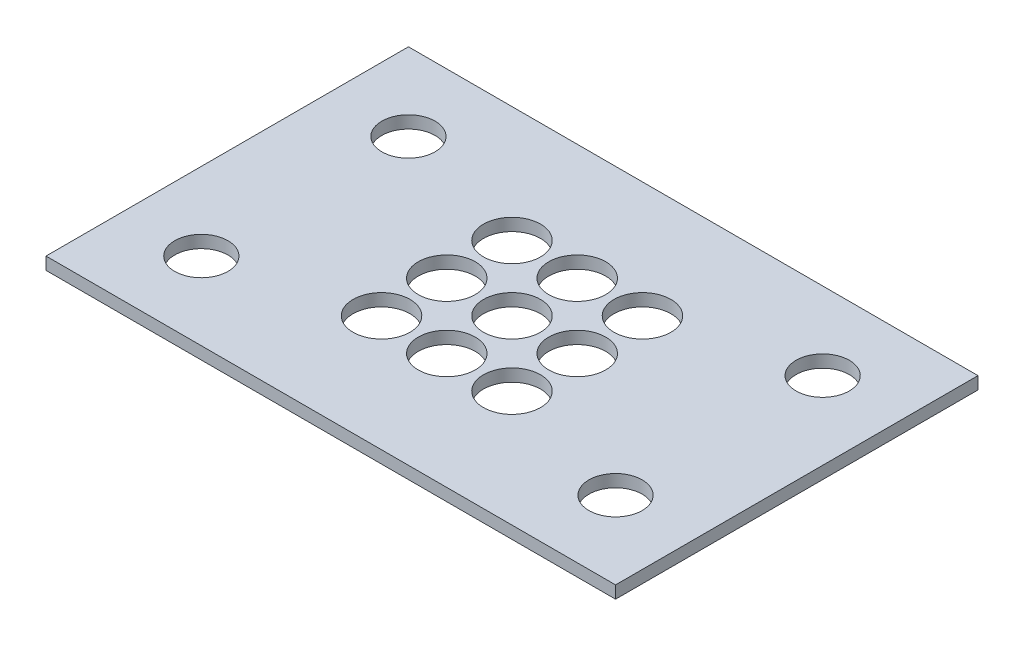
SolidWorks part; units mm, degrees
ref_plane "Front Plane" through (0, 0, 0) normal (0, 0, 1) x (1, 0, 0)
ref_plane "Top Plane" through (0, 0, 0) normal (0, 1, 0) x (1, 0, 0)
ref_plane "Right Plane" through (0, 0, 0) normal (1, 0, 0) x (0, 0, -1)
sketch "Sketch1" plane through (0, 0, 0) normal (0, 1, 0) x (1, 0, 0)
  line L0 (9.525, 34.925) -> (0, 34.925) construction
  line L1 (0, 0) -> (69.85, 0)
  line L2 (0, 0) -> (0, 44.45)
  line L3 (0, 44.45) -> (69.85, 44.45)
  line L4 (69.85, 0) -> (69.85, 44.45)
  line L5 (9.525, 34.925) -> (60.325, 34.925) construction
  line L6 (9.525, 34.925) -> (9.525, 9.525) construction
  line L7 (9.525, 9.525) -> (60.325, 9.525) construction
  line L8 (60.325, 34.925) -> (60.325, 9.525) construction
  line L9 (9.525, 34.925) -> (9.525, 44.45) construction
  circle A0 centre (9.525, 34.925) radius 3.2639
  circle A1 centre (60.325, 34.925) radius 3.2639
  circle A2 centre (9.525, 9.525) radius 3.2639
  circle A3 centre (60.325, 9.525) radius 3.2639
  circle A4 centre (34.925, 22.225) radius 3.4925
  circle A5 centre (42.925, 22.225) radius 3.4925
  circle A6 centre (42.925, 30.225) radius 3.4925
  circle A7 centre (34.925, 30.225) radius 3.4925
  circle A8 centre (42.925, 22.225) radius 3.4925
  circle A9 centre (42.925, 14.225) radius 3.4925
  circle A10 centre (34.925, 14.225) radius 3.4925
  circle A11 centre (26.925, 22.225) radius 3.4925
  circle A12 centre (26.925, 30.225) radius 3.4925
  circle A13 centre (34.925, 30.225) radius 3.4925
  circle A14 centre (26.925, 22.225) radius 3.4925
  circle A15 centre (26.925, 14.225) radius 3.4925
  circle A16 centre (34.925, 14.225) radius 3.4925
  point P13 (34.925, 34.925)
  point P14 (34.925, 44.45)
  point P20 (69.85, 22.225)
  dimension "D5" = 6.5278
  dimension "D6" = 6.985
  dimension "D1" = 69.85
  dimension "D2" = 44.45
  dimension "D3" = 50.8
  dimension "D4" = 25.4
  dimension "D15" = 8
  dimension "D16" = 8
  dimension "D7" = 2
  dimension "D8" = 2
  dimension "D9" = 2
  dimension "D10" = 2
  dimension "D11" = 2
  dimension "D12" = 2
  dimension "D13" = 2
  dimension "D14" = 2
extrude "Boss-Extrude1" add sketch "Sketch1" along normal blind 1.524 contours L1 L4 L3 L2 A15 A12 A11 A10 A9 A7 A6 A5 A4 A3 A2 A1 A0 region at (0.8279, 0, -22.225)
